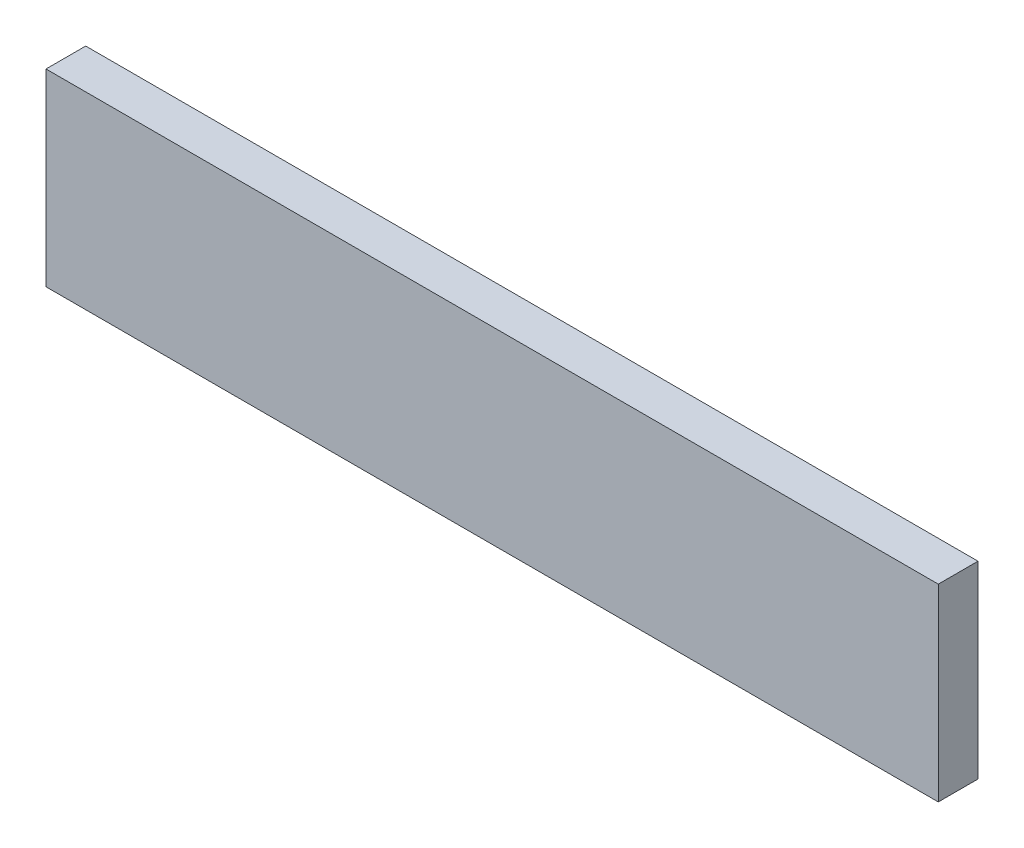
SolidWorks part; units mm, degrees
ref_plane "前视基准面" through (0, 0, 0) normal (0, 0, 1) x (1, 0, 0)
ref_plane "上视基准面" through (0, 0, 0) normal (0, 1, 0) x (1, 0, 0)
ref_plane "右视基准面" through (0, 0, 0) normal (1, 0, 0) x (0, 0, -1)
sketch "草图1" plane through (0, 0, 0) normal (0, 0, 1) x (1, 0, 0)
  line L0 (-51.5269, 0) -> (82.9283, 0) construction
  line L1 (0, 7.5) -> (71.3669, 7.5)
  line L2 (0, -7.5) -> (71.3669, -7.5)
  line L3 (71.3669, 7.5) -> (71.3669, 6.0168)
  line L4 (71.3669, 6.0168) -> (78.3669, 6.0168)
  line L5 (78.3669, 6.0168) -> (78.3669, 7.5)
  line L6 (78.3669, 7.5) -> (80.3669, 7.5)
  line L7 (80.3669, 7.5) -> (80.3669, -7.5)
  line L8 (78.3669, -7.5) -> (80.3669, -7.5)
  line L9 (78.3669, -6.0168) -> (78.3669, -7.5)
  line L10 (71.3669, -6.0168) -> (78.3669, -6.0168)
  line L11 (71.3669, -7.5) -> (71.3669, -6.0168)
  arc A1 (0, 7.5) -> (0, -7.5) centre (1.4961, 0) ccw
  point P14 (80.3669, 0)
  dimension "D2" = 15
  dimension "D3" = 1.4832
  dimension "D4" = 7
  dimension "D5" = 2
extrude "凸台-拉伸1" add sketch "草图1" along normal blind 2
sketch "草图2" plane through (0, 0, 2) normal (0, 0, 1) x (1, 0, 0)
  line L0 (0, 0) -> (80.3669, 0) construction
  line L1 (80.3669, -7.5) -> (80.3669, 7.5) construction
  line L2 (71.3669, 7.5) -> (0, 7.5) construction
  line L3 (2.25, 6) -> (3.75, 6)
  line L4 (2.25, 6) -> (2.25, -6)
  line L5 (2.25, -6) -> (3.75, -6)
  line L6 (3.75, 6) -> (3.75, -6)
  line L7 (2.25, 6) -> (3.75, -6) construction
  line L8 (2.25, -6) -> (3.75, 6) construction
  line L9 (5.25, 6) -> (5.25, -6)
  line L10 (5.25, 6) -> (6.75, 6)
  line L11 (6.75, 6) -> (6.75, -6)
  line L12 (5.25, -6) -> (6.75, -6)
  line L13 (8.25, 6) -> (8.25, -6)
  line L14 (8.25, 6) -> (9.75, 6)
  line L15 (9.75, 6) -> (9.75, -6)
  line L16 (8.25, -6) -> (9.75, -6)
  line L17 (11.25, 6) -> (11.25, -6)
  line L18 (11.25, 6) -> (12.75, 6)
  line L19 (12.75, 6) -> (12.75, -6)
  line L20 (11.25, -6) -> (12.75, -6)
  line L21 (14.25, 6) -> (14.25, -6)
  line L22 (14.25, 6) -> (15.75, 6)
  line L23 (15.75, 6) -> (15.75, -6)
  line L24 (14.25, -6) -> (15.75, -6)
  line L25 (17.25, 6) -> (17.25, -6)
  line L26 (17.25, 6) -> (18.75, 6)
  line L27 (18.75, 6) -> (18.75, -6)
  line L28 (17.25, -6) -> (18.75, -6)
  line L29 (20.25, 6) -> (20.25, -6)
  line L30 (20.25, 6) -> (21.75, 6)
  line L31 (21.75, 6) -> (21.75, -6)
  line L32 (20.25, -6) -> (21.75, -6)
  line L33 (23.25, 6) -> (23.25, -6)
  line L34 (23.25, 6) -> (24.75, 6)
  line L35 (24.75, 6) -> (24.75, -6)
  line L36 (23.25, -6) -> (24.75, -6)
  line L37 (26.25, 6) -> (26.25, -6)
  line L38 (26.25, 6) -> (27.75, 6)
  line L39 (27.75, 6) -> (27.75, -6)
  line L40 (26.25, -6) -> (27.75, -6)
  line L41 (29.25, 6) -> (29.25, -6)
  line L42 (29.25, 6) -> (30.75, 6)
  line L43 (30.75, 6) -> (30.75, -6)
  line L44 (29.25, -6) -> (30.75, -6)
  line L45 (32.25, 6) -> (32.25, -6)
  line L46 (32.25, 6) -> (33.75, 6)
  line L47 (33.75, 6) -> (33.75, -6)
  line L48 (32.25, -6) -> (33.75, -6)
  line L49 (35.25, 6) -> (35.25, -6)
  line L50 (35.25, 6) -> (36.75, 6)
  line L51 (36.75, 6) -> (36.75, -6)
  line L52 (35.25, -6) -> (36.75, -6)
  line L53 (38.25, 6) -> (38.25, -6)
  line L54 (38.25, 6) -> (39.75, 6)
  line L55 (39.75, 6) -> (39.75, -6)
  line L56 (38.25, -6) -> (39.75, -6)
  line L57 (41.25, 6) -> (41.25, -6)
  line L58 (41.25, 6) -> (42.75, 6)
  line L59 (42.75, 6) -> (42.75, -6)
  line L60 (41.25, -6) -> (42.75, -6)
  line L61 (44.25, 6) -> (44.25, -6)
  line L62 (44.25, 6) -> (45.75, 6)
  line L63 (45.75, 6) -> (45.75, -6)
  line L64 (44.25, -6) -> (45.75, -6)
  line L65 (47.25, 6) -> (47.25, -6)
  line L66 (47.25, 6) -> (48.75, 6)
  line L67 (48.75, 6) -> (48.75, -6)
  line L68 (47.25, -6) -> (48.75, -6)
  line L69 (50.25, 6) -> (50.25, -6)
  line L70 (50.25, 6) -> (51.75, 6)
  line L71 (51.75, 6) -> (51.75, -6)
  line L72 (50.25, -6) -> (51.75, -6)
  line L73 (53.25, 6) -> (53.25, -6)
  line L74 (53.25, 6) -> (54.75, 6)
  line L75 (54.75, 6) -> (54.75, -6)
  line L76 (53.25, -6) -> (54.75, -6)
  line L77 (56.25, 6) -> (56.25, -6)
  line L78 (56.25, 6) -> (57.75, 6)
  line L79 (57.75, 6) -> (57.75, -6)
  line L80 (56.25, -6) -> (57.75, -6)
  line L81 (59.25, 6) -> (59.25, -6)
  line L82 (59.25, 6) -> (60.75, 6)
  line L83 (60.75, 6) -> (60.75, -6)
  line L84 (59.25, -6) -> (60.75, -6)
  line L85 (62.25, 6) -> (62.25, -6)
  line L86 (62.25, 6) -> (63.75, 6)
  line L87 (63.75, 6) -> (63.75, -6)
  line L88 (62.25, -6) -> (63.75, -6)
  line L89 (65.25, 6) -> (65.25, -6)
  line L90 (65.25, 6) -> (66.75, 6)
  line L91 (66.75, 6) -> (66.75, -6)
  line L92 (65.25, -6) -> (66.75, -6)
  line L93 (68.25, 6) -> (68.25, -6)
  line L94 (68.25, 6) -> (69.75, 6)
  line L95 (69.75, 6) -> (69.75, -6)
  line L96 (68.25, -6) -> (69.75, -6)
  point P5 (3, 0)
  dimension "D1" = 3
  dimension "D2" = 1.5
  dimension "D3" = 1.5
  dimension "D4" = 23
extrude "凸台-拉伸2" add sketch "草图2" along normal blind 1
sketch "草图3" plane through (0, 0, 0) normal (0, 0, -1) x (-1, 0, 0)
  line L0 (-71.3669, 7.5) -> (0, 7.5) construction
  line L1 (-82.3669, 9.5) -> (7.5, 9.5)
  line L2 (-82.3669, 9.5) -> (-82.3669, -9.5)
  line L3 (-82.3669, -9.5) -> (7.5, -9.5)
  line L4 (7.5, 9.5) -> (7.5, -9.5)
  line L5 (-80.3669, -7.5) -> (-80.3669, 7.5) construction
  line L6 (0, -7.5) -> (-71.3669, -7.5) construction
  dimension "D1" = 2
  dimension "D2" = 2
  dimension "D3" = 2
  dimension "D4" = 7.5
extrude "凸台-拉伸3" add sketch "草图3" against normal blind 4 separate body
combine bodies "组合1" operation type subtract main body 103 bodies to subtract 102
scale "缩放比例1" scale about centroid uniform scaling yes scale factor 1.6
